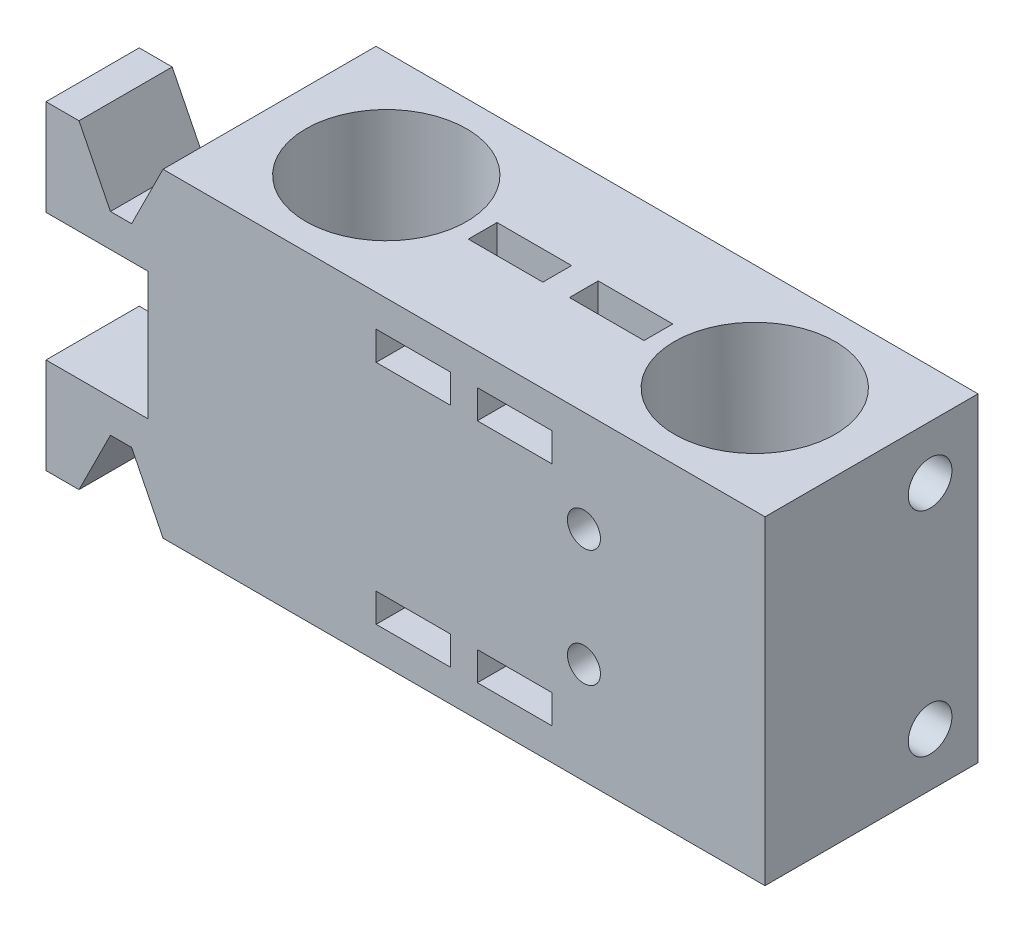
SolidWorks part; units mm, degrees
ref_plane "Front Plane" through (0, 0, 0) normal (0, 0, 1) x (1, 0, 0)
ref_plane "Top Plane" through (0, 0, 0) normal (0, 1, 0) x (1, 0, 0)
ref_plane "Right Plane" through (0, 0, 0) normal (1, 0, 0) x (0, 0, -1)
sketch "BackFace-Sketch1" plane through (0, 0, 0) normal (0, 0, 1) x (1, 0, 0)
  line L0 (0, 0) -> (0, 9)
  line L1 (0, 9) -> (9.6, 9)
  line L2 (9.6, 9) -> (9.6, 21)
  line L3 (9.6, 21) -> (0, 21)
  line L4 (0, 21) -> (0, 30)
  line L5 (0, 30) -> (3.1, 30)
  line L6 (3.1, 30) -> (6.05, 24.096)
  line L7 (6.05, 24.096) -> (8.04, 24.096)
  line L8 (8.04, 24.096) -> (10.99, 30)
  line L9 (10.99, 30) -> (67.51, 30)
  line L10 (67.51, 30) -> (67.51, 0)
  line L12 (10.99, 0) -> (8.04, 5.904)
  line L13 (8.04, 5.904) -> (6.05, 5.904)
  line L14 (6.05, 5.904) -> (3.1, 0)
  line L15 (3.1, 0) -> (0, 0)
  line L23 (67.51, 0) -> (10.99, 0)
  point P13 (4.8, 9)
  point P17 (4.575, 2.952)
  point P18 (7.045, 24.096)
  point P19 (7.045, 5.904)
  dimension "D1" = 3.1
  dimension "D4" = 6.6
  dimension "D5" = 1.99
  dimension "D7" = 30
  dimension "D8" = 9.6
  dimension "D6" = 2.95
  dimension "D12" = 57.91
  dimension "D3" = 56.52
  dimension "D9" = 6.6
extrude "Boss-Extrude1" add sketch "BackFace-Sketch1" along normal blind 20
sketch "EarKnotch-Sketch2" plane through (0, 0, 0) normal (0, 0, -1) x (-1, 0, 0)
  line L0 (-67.51, 30) -> (-10.99, 30) construction
  line L1 (0, 30) -> (-10.99, 30)
  line L2 (0, 30) -> (0, 0)
  line L3 (0, 0) -> (-10.99, 0)
  line L4 (-10.99, 30) -> (-10.99, 0)
  line L8 (0, 30) -> (0, 21) construction
extrude "EarKnotch-Cut-Extrude1" cut sketch "EarKnotch-Sketch2" against normal blind 11.25
sketch "TopHoles-Sketch3" plane through (0, 0, 0) normal (-1, 0, 0) x (0, 0, 1)
  line L0 (20, 30) -> (20, 21) construction
  line L1 (20, 30) -> (11.25, 30) construction
  line L2 (20, 0) -> (11.25, 0) construction
  circle A0 centre (15.5, 25.5) radius 2.05
  circle A1 centre (15.5, 4.5) radius 2.05
  dimension "D4" = 4.1
  dimension "D1" = 4.5
  dimension "D2" = 4.5
  dimension "D3" = 4.5
extrude "TopHoles-Cut-Extrude2" cut sketch "TopHoles-Sketch3" against normal blind 4
sketch "FrontHoles-Sketch1" plane through (0, 0, 0) normal (0, 0, -1) x (-1, 0, 0)
  line L0 (-67.51, 0) -> (-67.51, 30) construction
  line L1 (-67.51, 30) -> (-10.99, 30) construction
  line L3 (-10.99, 0) -> (-67.51, 0) construction
  circle A0 centre (-43.86, 25) radius 2.05
  circle A1 centre (-43.86, 5) radius 2.05
  circle A2 centre (-31.86, 25) radius 2.05
  circle A3 centre (-31.86, 5) radius 2.05
  dimension "D2" = 4.1
  dimension "D1" = 23.65
  dimension "D3" = 12
  dimension "D5" = 5
extrude "FrontHoles-Cut-Extrude1" cut sketch "FrontHoles-Sketch1" against normal blind 7
sketch "RearRibbonHoles-Sketch2" plane through (0, 0, 20) normal (0, 0, 1) x (1, 0, 0)
  line L1 (31, 27) -> (38, 27)
  line L2 (31, 27) -> (31, 24.3)
  line L3 (31, 24.3) -> (38, 24.3)
  line L4 (38, 27) -> (38, 24.3)
  line L5 (40.5, 27) -> (47.5, 27)
  line L6 (40.5, 27) -> (40.5, 24.3)
  line L7 (40.5, 24.3) -> (47.5, 24.3)
  line L8 (47.5, 27) -> (47.5, 24.3)
  line L9 (31, 5.7) -> (38, 5.7)
  line L10 (31, 5.7) -> (31, 3)
  line L11 (31, 3) -> (38, 3)
  line L12 (38, 5.7) -> (38, 3)
  line L13 (40.5, 5.7) -> (47.5, 5.7)
  line L14 (40.5, 5.7) -> (40.5, 3)
  line L15 (40.5, 3) -> (47.5, 3)
  line L16 (47.5, 5.7) -> (47.5, 3)
  line L18 (67.51, 30) -> (10.99, 30) construction
  line L19 (10.99, 0) -> (67.51, 0) construction
  line L22 (67.51, 0) -> (67.51, 30) construction
  dimension "D3" = 2.7
  dimension "D5" = 2.5
  dimension "D2" = 3
  dimension "D7" = 20.01
  dimension "D6" = 20.01
extrude "RearRibbonHoles-Cut-Extrude1" cut sketch "RearRibbonHoles-Sketch2" against normal blind 11.35
sketch "LeftRibbonHoles-Sketch3" plane through (0, 0, 0) normal (0, -1, 0) x (1, 0, 0)
  line L0 (31, 8.65) -> (38, 8.65) construction
  line L1 (31, 11.35) -> (38, 11.35)
  line L2 (31, 11.35) -> (31, 8.65)
  line L3 (31, 8.65) -> (38, 8.65)
  line L4 (38, 11.35) -> (38, 8.65)
  line L5 (40.5, 11.35) -> (47.5, 11.35)
  line L6 (40.5, 11.35) -> (40.5, 8.65)
  line L7 (40.5, 8.65) -> (47.5, 8.65)
  line L8 (47.5, 11.35) -> (47.5, 8.65)
  line L9 (31, 8.65) -> (31, 20) construction
  line L10 (38, 8.65) -> (38, 20) construction
  line L11 (40.5, 8.65) -> (40.5, 20) construction
  line L12 (47.5, 8.65) -> (47.5, 20) construction
  dimension "D1" = 2.7
sketch "RightRibbonHoles-Sketch4" plane through (0, 30, 0) normal (0, 1, 0) x (1, 0, 0)
  line L0 (47.5, -8.65) -> (40.5, -8.65) construction
  line L9 (38, -8.65) -> (31, -8.65) construction
  line L10 (31, -8.65) -> (31, -20) construction
  line L11 (40.5, -8.65) -> (40.5, -20) construction
  line L12 (67.51, -20) -> (10.99, -20) construction
  line L13 (47.5, -8.65) -> (47.5, -20) construction
  line L14 (31, -8.65) -> (38, -8.65)
  line L15 (31, -8.65) -> (31, -11.35)
  line L16 (31, -11.35) -> (38, -11.35)
  line L17 (38, -8.65) -> (38, -11.35)
  line L18 (40.5, -8.65) -> (47.5, -8.65)
  line L19 (40.5, -8.65) -> (40.5, -11.35)
  line L20 (40.5, -11.35) -> (47.5, -11.35)
  line L21 (47.5, -8.65) -> (47.5, -11.35)
  line L22 (38, -8.65) -> (38, -20) construction
  line L23 (38, -8.65) -> (31, -8.65) construction
  line L26 (55.51, -26.7) -> (33.1572, -26.7) construction
  line L27 (50.99, -27.35) -> (33.1572, -27.35) construction
  dimension "D1" = 2.7
  dimension "D2" = 8.65
extrude "RightRibbonHoles-Cut-Extrude2" cut sketch "RightRibbonHoles-Sketch4" against normal blind 5.7
extrude "LeftRibbonHoles-Cut-Extrude2" cut sketch "LeftRibbonHoles-Sketch3" against normal blind 5.7
sketch "BottomClampMountingHolesSketch3" plane through (67.51, 0, 0) normal (1, 0, 0) x (0, 0, -1)
  line L2 (-20, 0) -> (0, 0) construction
  line L3 (-20, 30) -> (0, 30) construction
  line L4 (0, 0) -> (0, 30) construction
  circle A0 centre (-4.5, 25) radius 2.05
  circle A1 centre (-4.5, 5) radius 2.05
  dimension "D1" = 4.1
  dimension "D4" = 4.5
extrude "BottomClampMountHolesCut-Extrude1" cut sketch "BottomClampMountingHolesSketch3" against normal blind 4
sketch "LM8UUHolesSketch1" plane through (0, 30, 0) normal (0, 1, 0) x (1, 0, 0)
  line L0 (67.51, 0) -> (10.99, 0) construction
  line L1 (67.51, -20) -> (67.51, 0) construction
  line L2 (10.99, -11.25) -> (10.99, 0) construction
  circle A0 centre (21.95, -10) radius 7.55
  circle A1 centre (56.55, -10) radius 7.55
  point P9 (67.51, -10)
  dimension "D1" = 15.1
  dimension "D3" = 34.6
  dimension "D4" = 10.96
  dimension "D5" = 10.96
  dimension "D6" = 56.52
extrude "LM8UUCut-Extrude1" cut sketch "LM8UUHolesSketch1" against normal through all
fillet "RibbonHoleFillet2" radius 2.7 1 edges at (34.5, 5.7, 8.65)
fillet "RibbonHoleFillet1" radius 2.7 1 edges at (44, 5.7, 8.65)
fillet "RibbonHoleFillet3" radius 2.7 1 edges at (44, 24.3, 8.65)
fillet "RibbonHoleFillet4" radius 2.7 1 edges at (34.5, 24.3, 8.65)
sketch "ProbeMountingHolesSketch1" plane through (0, 0, 20) normal (0, 0, 1) x (1, 0, 0)
  line L0 (67.51, 30) -> (10.99, 30) construction
  line L1 (10.99, 0) -> (67.51, 0) construction
  line L2 (67.51, 0) -> (67.51, 30) construction
  circle A0 centre (50.51, 20.5) radius 1.55
  circle A1 centre (50.51, 9.5) radius 1.55
  dimension "D4" = 3.1
  dimension "D2" = 9.5
  dimension "D3" = 17
  dimension "D5" = 9.5
extrude "ProbeMountingHolesCut-Extrude1" cut sketch "ProbeMountingHolesSketch1" against normal blind 3.1
sketch "LM8UUFasteningHoleSketch1" plane through (0, 0, 0) normal (0, 0, -1) x (-1, 0, 0)
  line L0 (-56.55, 0) -> (-56.55, 30) construction
  line L1 (-21.95, 0) -> (-21.95, 30) construction
  line L2 (-67.51, 30) -> (-10.99, 30) construction
  circle A0 centre (-30.55, 15) radius 2.1
  circle A1 centre (-47.95, 15) radius 2.1
  dimension "D4" = 4.2
  dimension "D1" = 8.6
  dimension "D3" = 15
extrude "LM8UUFasteningHoleCut-Extrude1" cut sketch "LM8UUFasteningHoleSketch1" against normal blind 14
equation "\"LinearGBWidth\"= 27mm'Spec"
equation "\"CarrierRibbonHoleWidth\"= 7mm"
equation "\"CarrierRibbonHoleHeight\"= 2.7mm"
equation "\"CarrierRibbonHoleDistance\"= 2.5mm'Equals 2.5. Must equal distance created by GABRiserBossOffset"
equation "\"CarrierRibbonHoleOffsetFromSide\"= 3.0mm"
equation "\"CarrierDepth\"= 20mm'From the100"
equation "\"D1@Boss-Extrude1\"=\"CarrierDepth\""
equation "\"D3@RearRibbonHoles-Sketch2\" = \"CarrierRibbonHoleHeight\""
equation "\"D4@RearRibbonHoles-Sketch2\" = \"CarrierRibbonHoleWidth\""
equation "\"D5@RearRibbonHoles-Sketch2\" = \"CarrierRibbonHoleDistance\""
equation "\"D1@RightRibbonHoles-Cut-Extrude2\" = \"CarrierRibbonHoleOffsetFromSide\" + \"CarrierRibbonHoleHeight\""
equation "\"D1@LeftRibbonHoles-Cut-Extrude2\" = \"CarrierRibbonHoleOffsetFromSide\" + \"CarrierRibbonHoleHeight\""
equation "\"D1@RightRibbonHoles-Sketch4\"=\"CarrierRibbonHoleHeight\""
equation "\"D1@RearRibbonHoles-Cut-Extrude1\"=\"CarrierDepth\" / 2 + \"CarrierRibbonHoleHeight\"/2"
equation "\"D1@LeftRibbonHoles-Sketch3\"=\"CarrierRibbonHoleHeight\""
equation "\"AngledCarrierBodyLength\"= \"CarrierBodyLength\" - 1.39mm'From the 100 1.39 accounts for the little slant"
equation "\"M3HeatInsertHoleDiameter\"= 4mm + .1mm'Add .1mm for printing"
equation "\"D1@BottomClampMountingHolesSketch3\"=\"M3HeatInsertHoleDiameter\""
equation "\"M3HeatInsertHoleDepth\"= 4mm"
equation "\"D1@BottomClampMountHolesCut-Extrude1\"=\"M3HeatInsertHoleDepth\""
equation "\"D1@RibbonHoleFillet1\" = \"CarrierRibbonHoleHeight\""
equation "\"D1@RibbonHoleFillet2\"=\"CarrierRibbonHoleHeight\""
equation "\"D1@RibbonHoleFillet3\"=\"CarrierRibbonHoleHeight\""
equation "\"D1@RibbonHoleFillet4\"=\"CarrierRibbonHoleHeight\""
equation "\"D4@TopHoles-Sketch3\"=\"M3HeatInsertHoleDiameter\""
equation "\"D2@FrontHoles-Sketch1\"=\"M3HeatInsertHoleDiameter\""
equation "\"D3@BackFace-Sketch1\"= \"AngledCarrierBodyLength\""
equation "\"D1@RearRibbonHoles-Sketch2\"=\"CarrierRibbonHoleOffsetFromSide\""
equation "\"D2@RearRibbonHoles-Sketch2\"=\"CarrierRibbonHoleOffsetFromSide\""
equation "\"D2@LM8UUHolesSketch1\"=\"CarrierDepth\" / 2 "
equation "\"GABDistanceBetweenXAxisRods\"= 34.6mm'From the100"
equation "\"D3@LM8UUHolesSketch1\"=\"GABDistanceBetweenXAxisRods\""
equation "\"LM8UUDiameter\"= 15mm"
equation "\"D1@LM8UUHolesSketch1\"=\"LM8UUDiameter\" + .1mm"
equation "\"CarrierBodyLength\"= 57.91mm"
equation "\"D4@LM8UUHolesSketch1\" = ( \"AngledCarrierBodyLength\" - \"GABDistanceBetweenXAxisRods\" ) / 2"
equation "\"D6@RearRibbonHoles-Sketch2\"=(\"AngledCarrierBodyLength\" - \"CarrierRibbonHoleWidth\" * 2 - \"CarrierRibbonHoleDistance\")/2"
equation "\"CarrierWidth\"= 30mm"
equation "\"D7@BackFace-Sketch1\"=\"CarrierWidth\""
equation "\"D2@ProbeMountingHolesSketch1\" =  ( \"CarrierWidth\" - \"ProbeDistanceBetweenMountingHoles\" )  / 2"
equation "\"M2HeatInsertHoleDiameter\"= 3mm + .1mm'Add .1mm for printing"
equation "\"M2HeatInsertHoleDepth\"= 3.1mm'Spec"
equation "\"D4@ProbeMountingHolesSketch1\" = \"M2HeatInsertHoleDiameter\""
equation "\"D1@ProbeMountingHolesCut-Extrude1\" = \"M2HeatInsertHoleDepth\""
equation "\"ProbeDistanceBetweenMountingHoles\" = 11mm"
equation "\"D1@ProbeMountingHolesSketch1\" = \"ProbeDistanceBetweenMountingHoles\""
equation "\"LM8UUFasteningHoleDiameter\"= 4.2mm'10/24 set screw hole diameter"
equation "\"D1@LM8UUFasteningHoleSketch1\" = \"LM8UUDiameter\" / 2 + \"LM8UUFasteningHoleDiameter\" / 2 - 1mm"
equation "\"D2@LM8UUFasteningHoleSketch1\" = \"LM8UUDiameter\" / 2 + \"LM8UUFasteningHoleDiameter\" / 2 - 1mm"
equation "\"D3@LM8UUFasteningHoleSketch1\" = \"CarrierWidth\" / 2"
equation "\"D1@LM8UUFasteningHoleCut-Extrude1\"= \"CarrierDepth\" / 2 + 4mm'Odd that up to next does not work properly"
